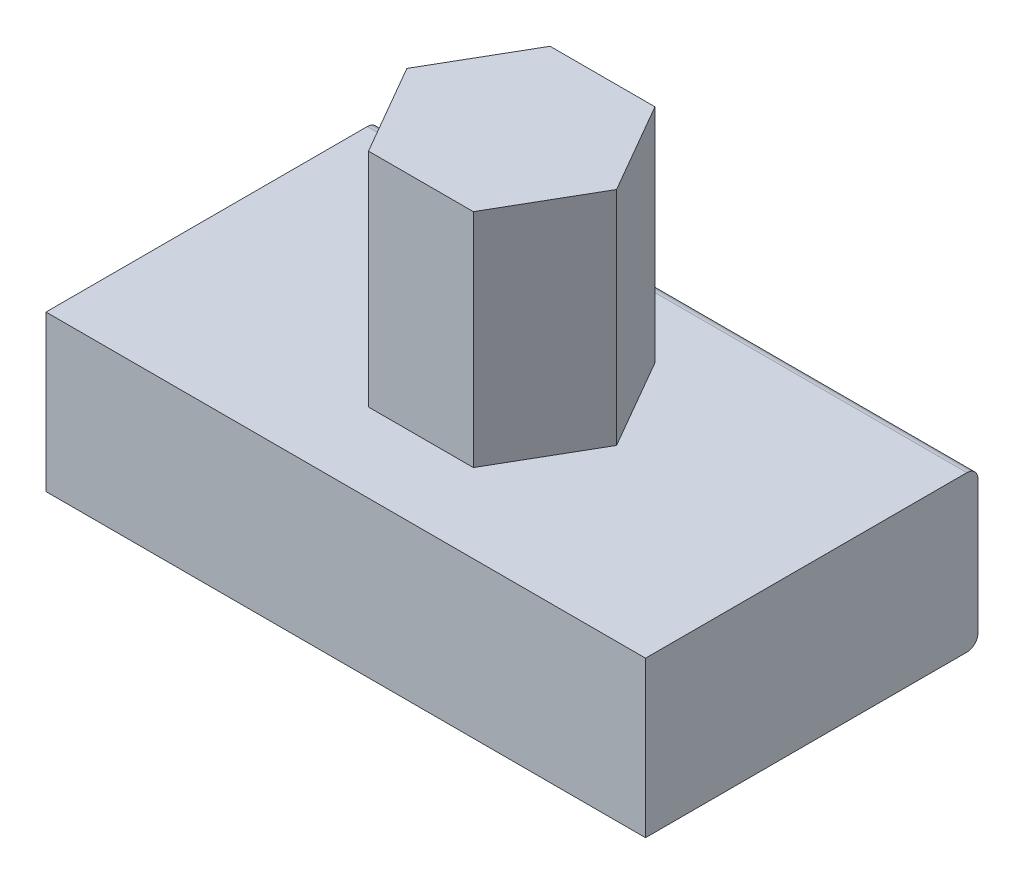
SolidWorks part; units mm, degrees
ref_plane "Front Plane" through (0, 0, 0) normal (0, 0, 1) x (1, 0, 0)
ref_plane "Top Plane" through (0, 0, 0) normal (0, 1, 0) x (1, 0, 0)
ref_plane "Right Plane" through (0, 0, 0) normal (1, 0, 0) x (0, 0, -1)
sketch "Sketch1" plane through (0, 0, 0) normal (0, 0, 1) x (1, 0, 0)
  line L1 (-68.7035, -17.821) -> (68.7035, -17.821)
  line L2 (-68.7035, -17.821) -> (-68.7035, 17.821)
  line L3 (-68.7035, 17.821) -> (68.7035, 17.821)
  line L4 (68.7035, -17.821) -> (68.7035, 17.821)
  line L5 (-68.7035, -17.821) -> (68.7035, 17.821) construction
  line L6 (-68.7035, 17.821) -> (68.7035, -17.821) construction
  point P0 (0, 0)
extrude "Boss-Extrude1" add sketch "Sketch1" along normal blind 76.2 contours L1 L4 L3 L2
sketch "Sketch2" plane through (0, 17.821, 0) normal (0, 1, 0) x (1, 0, 0)
  line L1 (23.159, -37.2907) -> (11.1437, -16.4796)
  line L2 (11.1437, -16.4796) -> (-12.8869, -16.4796)
  line L3 (-12.8869, -16.4796) -> (-24.9022, -37.2907)
  line L4 (-24.9022, -37.2907) -> (-12.8869, -58.1018)
  line L5 (-12.8869, -58.1018) -> (11.1437, -58.1018)
  line L6 (11.1437, -58.1018) -> (23.159, -37.2907)
  circle A0 centre (-0.8716, -37.2907) radius 20.8111 construction
extrude "Boss-Extrude2" add sketch "Sketch2" along normal blind 50.8
sketch "Sketch4" plane through (0, 0, 76.2) normal (0, 0, 1) x (1, 0, 0)
  line L1 (-52.1439, 14.8868) -> (-17.3813, 14.8868)
  line L2 (-52.1439, 14.8868) -> (-52.1439, 8.1274)
  line L3 (-52.1439, 8.1274) -> (-17.3813, 8.1274)
  line L4 (-17.3813, 14.8868) -> (-17.3813, 8.1274)
  line L5 (-52.1439, 14.8868) -> (-17.3813, 8.1274) construction
  line L6 (-52.1439, 8.1274) -> (-17.3813, 14.8868) construction
  line L7 (2.2531, 8.2883) -> (41.2001, 8.2883)
  line L8 (2.2531, 8.2883) -> (2.2531, -6.1961)
  line L9 (2.2531, -6.1961) -> (41.2001, -6.1961)
  line L10 (41.2001, 8.2883) -> (41.2001, -6.1961)
  line L11 (2.2531, 8.2883) -> (41.2001, -6.1961) construction
  line L12 (2.2531, -6.1961) -> (41.2001, 8.2883) construction
  point P0 (-34.7626, 11.5071)
  point P5 (21.7266, 1.0461)
fillet "Fillet2" radius 2.54 2 edges at (0, -17.821, 0) (0, 17.821, 0)
